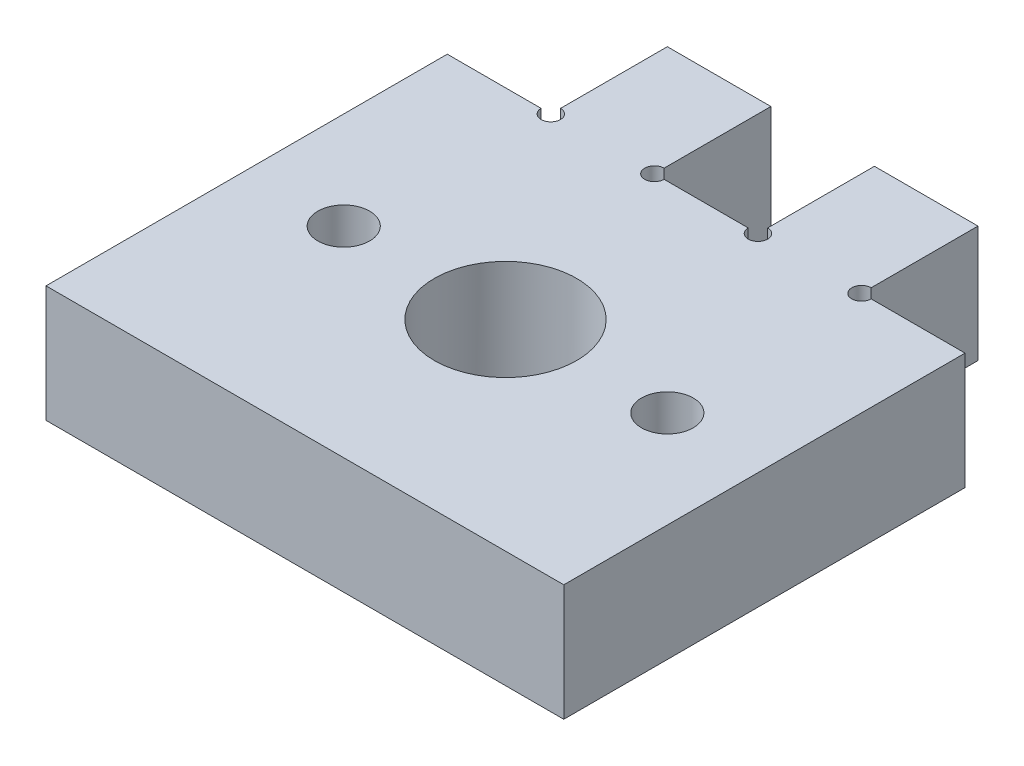
SolidWorks part; units mm, degrees
ref_plane "Front Plane" through (0, 0, 0) normal (0, 0, 1) x (1, 0, 0)
ref_plane "Top Plane" through (0, 0, 0) normal (0, 1, 0) x (1, 0, 0)
ref_plane "Right Plane" through (0, 0, 0) normal (1, 0, 0) x (0, 0, -1)
sketch "Sketch1" plane through (0, 0, 0) normal (0, 1, 0) x (1, 0, 0)
  line L0 (-1000, 0) -> (49000, 0) construction
  line L5 (0, -1000) -> (0, 49000) construction
  line L6 (-40, 31) -> (-24, 31)
  line L7 (-40, -31) -> (40, -31)
  line L8 (-40, -31) -> (-40, 31)
  line L9 (-24, 49) -> (-8, 49)
  line L10 (40, -31) -> (40, 31)
  line L11 (-24, 49) -> (-24, 31)
  line L12 (-8, 49) -> (-8, 31)
  line L13 (8, 49) -> (8, 31)
  line L14 (24, 49) -> (24, 31)
  line L16 (24, 31) -> (40, 31)
  line L17 (8, 49) -> (24, 49)
  line L18 (-8, 31) -> (8, 31)
  circle A10 centre (0, 0) radius 4
  circle A15 centre (25, 0) radius 4
  circle A16 centre (-25, 0) radius 4
  point P6 (0, 31)
  point P10 (-40, 0)
  dimension "D3" = 8
  dimension "D12" = 8
  dimension "D2" = 80
  dimension "D7" = 18
  dimension "D9" = 4
  dimension "D8" = 16
  dimension "D10" = 16
  dimension "D11" = 80
  dimension "D13" = 25
extrude "Boss-Extrude1" add sketch "Sketch1" along normal blind 18
sketch "Sketch2" plane through (0, 18, 0) normal (0, 1, 0) x (1, 0, 0)
  circle A0 centre (0, 0) radius 11
  dimension "D1" = 22
extrude "Cut-Extrude1" cut sketch "Sketch2" against normal up to next
sketch "Sketch3" plane through (0, 18, 0) normal (0, 1, 0) x (1, 0, 0)
  circle A0 centre (-24, 31) radius 1.5
  circle A1 centre (-8, 31) radius 1.5
  circle A2 centre (8, 31) radius 1.5
  circle A3 centre (24, 31) radius 1.5
  dimension "D1" = 3
  dimension "D3" = 16
  dimension "D2" = 4
extrude "Cut-Extrude2" cut sketch "Sketch3" against normal through all
